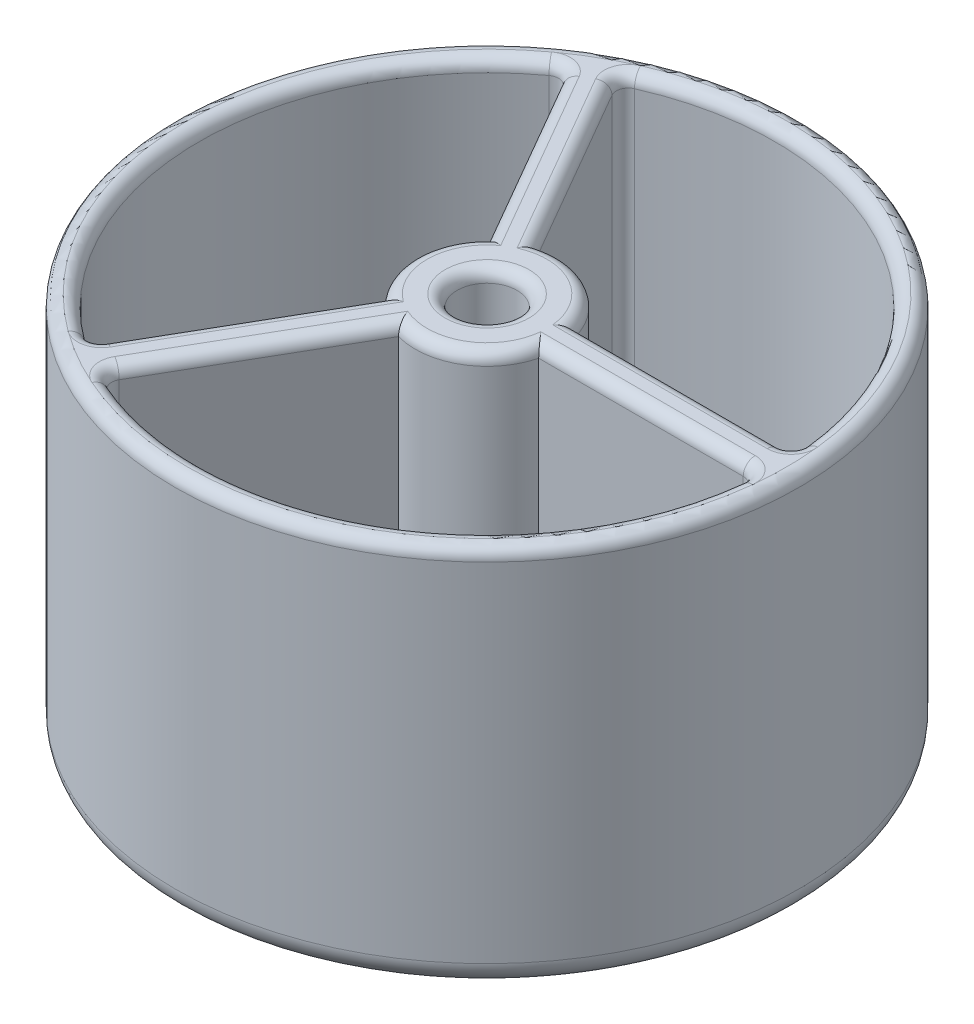
SolidWorks part; units mm, degrees
material "ABS"
ref_plane "Front Plane" through (0, 0, 0) normal (0, 0, 1) x (1, 0, 0)
ref_plane "Top Plane" through (0, 0, 0) normal (0, 1, 0) x (1, 0, 0)
ref_plane "Right Plane" through (0, 0, 0) normal (1, 0, 0) x (0, 0, -1)
sketch "Sketch1" plane through (0, 0, 0) normal (0, 1, 0) x (1, 0, 0)
  circle A0 centre (0, 0) radius 13
  dimension "D1" = 26
extrude "Boss-Extrude1" add sketch "Sketch1" along normal blind 16
sketch "Sketch2" plane through (0, 16, 0) normal (0, 1, 0) x (1, 0, 0)
  circle A0 centre (0, 0) radius 12
  dimension "D1" = 24
extrude "Cut-Extrude1" cut sketch "Sketch2" against normal blind 15
sketch "Sketch3" plane through (0, 1, 0) normal (0, 1, 0) x (1, 0, 0)
  circle A0 centre (0, 0) radius 1.25
  circle A1 centre (0, 0) radius 3
  dimension "D1" = 2.5
extrude "Boss-Extrude3" add sketch "Sketch3" along normal blind 15
sketch "Sketch5" plane through (0, 1, 0) normal (0, 1, 0) x (1, 0, 0)
  line L2 (-0.6495, 2.625) -> (-1.9486, 1.875)
  line L4 (-1.9486, -1.875) -> (-0.6495, -2.625)
  line L6 (2.5981, -0.75) -> (2.5981, 0.75)
  line L15 (-1.299, -2.25) -> (-0.6495, -2.625)
  line L16 (-1.299, -2.25) -> (-1.9486, -1.875)
  line L17 (-1.299, 2.25) -> (-0.6495, 2.625)
  line L18 (-1.299, 2.25) -> (-1.9486, 1.875)
  line L19 (2.5981, 0) -> (2.5981, -0.75)
  line L20 (2.5981, 0) -> (2.5981, 0.75)
  line L21 (2.5981, 0.75) -> (11.9765, 0.75)
  line L22 (2.5981, 1.5) -> (0, 3) [skipped]
  line L23 (-2.5981, 1.5) -> (-2.5981, -1.5) [skipped]
  line L24 (0, -3) -> (2.5981, -1.5) [skipped]
  line L25 (2.5981, -0.75) -> (11.9765, -0.75)
  line L26 (-1.9486, -1.875) -> (-6.6378, -9.997)
  line L27 (-0.6495, -2.625) -> (-5.3388, -10.747)
  line L28 (-1.9486, 1.875) -> (-6.6378, 9.997)
  line L29 (-0.6495, 2.625) -> (-5.3388, 10.747)
  circle A0 centre (0, 0) radius 12 construction
  arc A1 (-5.3388, 10.747) -> (-6.6378, 9.997) centre (0, 0) ccw
  arc A2 (11.9765, -0.75) -> (11.9765, 0.75) centre (0, 0) ccw
  arc A3 (-6.6378, -9.997) -> (-5.3388, -10.747) centre (0, 0) ccw
  circle A5 centre (0, 0) radius 12 construction
  point P23 (7.299, -0.375)
  point P26 (-4.1178, 6.0508)
  point P29 (-2.4743, -4.2856)
extrude "Boss-Extrude4" add sketch "Sketch5" along normal blind 15 contours L26 A3 L27 L4 | L25 A2 L21 L6 | L29 A1 L28 L2 region at (-3.6476, 1, -6.3178) region at (-3.6476, 1, 6.3178) region at (7.2951, 1, 0)
fillet "Fillet4" radius 0.5 6 edges at (-5.3388, 8.5, -10.747) (11.9765, 8.5, -0.75) (-6.6378, 8.5, -9.997) (11.9765, 8.5, 0.75) (-6.6378, 8.5, 9.997) (-5.3388, 8.5, 10.747)
fillet "Fillet8" radius 0.5 20 edges at (0, 16, 1.25) (0, 16, 13) (-2.9346, 16, 6.5829) (-5.1086, 16, 10.6808) (6, 16, 10.3923) (11.8041, 16, 0.9162) (7.1683, 16, 0.75) (1.5, 16, 2.5981) (7.1683, 16, -0.75) (11.8041, 16, -0.9162) (6, 16, -10.3923) (-5.1086, 16, -10.6808) (-2.9346, 16, -6.5829) (1.5, 16, -2.5981) (-6.6955, 16, -9.7646) (-12, 16, 0) (-6.6955, 16, 9.7646) (-4.2337, 16, 5.8329) (-3, 16, 0) (-4.2337, 16, -5.8329)
fillet "Fillet9" radius 0.5 18 edges at (-6.6955, 1, 9.7646) (11.8041, 1, -0.9162) (7.1683, 1, -0.75) (11.8041, 1, 0.9162) (7.1683, 1, 0.75) (-4.2337, 1, 5.8329) (-3, 1, 0) (-4.2337, 1, -5.8329) (-6.6955, 1, -9.7646) (-12, 1, 0) (6, 1, 10.3923) (-5.1086, 1, 10.6808) (-2.9346, 1, 6.5829) (1.5, 1, 2.5981) (6, 1, -10.3923) (-5.1086, 1, -10.6808) (1.5, 1, -2.5981) (-2.9346, 1, -6.5829)
fillet "Fillet10" radius 1 1 edges at (0, 0, 13)
